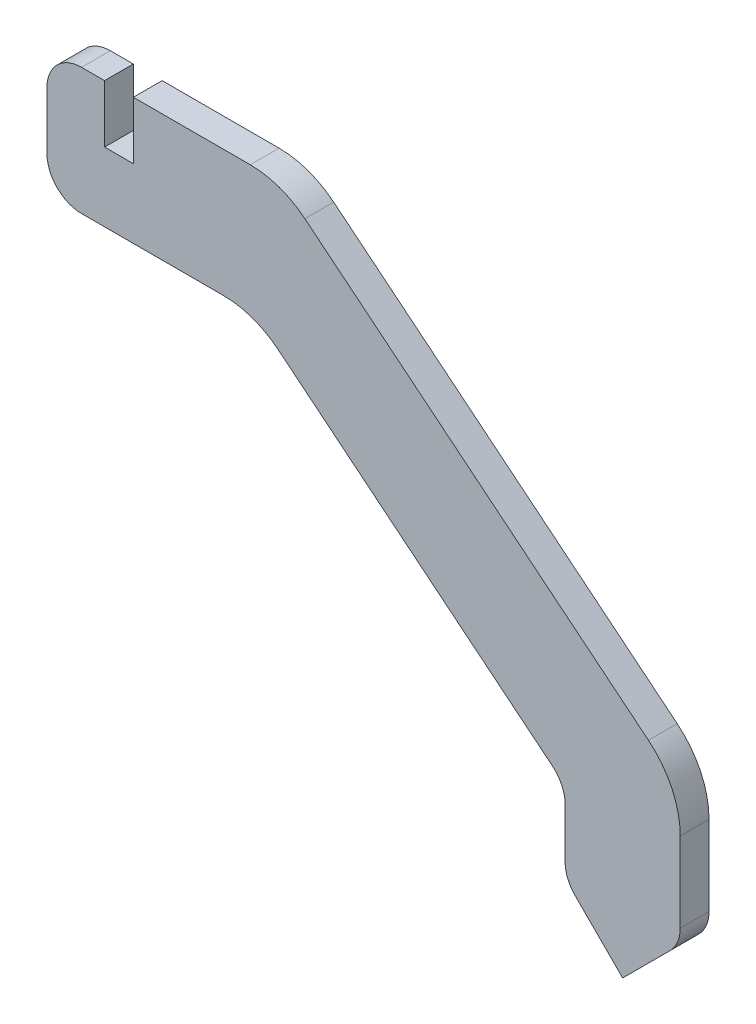
SolidWorks part; units mm, degrees
material "PBT General Purpose"
ref_plane "Front Plane" through (0, 0, 0) normal (0, 0, 1) x (1, 0, 0)
ref_plane "Top Plane" through (0, 0, 0) normal (0, 1, 0) x (1, 0, 0)
ref_plane "Right Plane" through (0, 0, 0) normal (1, 0, 0) x (0, 0, -1)
sketch "frame_outline" plane through (0, 0, 0) normal (0, 0, 1) x (1, 0, 0)
  line L127 (0, 0) -> (0, 1.1)
  line L128 (0, 1.1) -> (0.5, 1.1)
  line L129 (0.5, 1.1) -> (0.5, 0.6)
  line L130 (0.5, 0.6) -> (0.75, 0.6)
  line L131 (0.75, 0.6) -> (0.75, 1.1)
  line L132 (0.75, 1.1) -> (2.0331, 1.1)
  line L133 (2.0331, 1.1) -> (5.5, -1.7249)
  line L134 (5.5, -1.7249) -> (5.5, -2.9)
  line L135 (5.5, -2.9) -> (5, -3.4)
  line L136 (5, -3.4) -> (4.5, -2.9)
  line L137 (4.5, -2.9) -> (4.5, -2.2)
  line L138 (4.5, -2.2) -> (1.8, 0)
  line L139 (1.8, 0) -> (0, 0)
  dimension "D1" = 0.25
  dimension "D2" = 0.5
  dimension "D3" = 0.6
  dimension "D4" = 0.5
  dimension "D5" = 5
  dimension "D6" = 3.4
  dimension "D7" = 1
  dimension "D8" = 1
  dimension "D9" = 0.7
  dimension "D10" = 1.8
extrude "Boss-Extrude1" add sketch "frame_outline" along normal mid plane 0.25
fillet "Fillet1" radius 0.3 5 edges at (5.5, -2.9, 0) (4.5, -2.9, 0) (0, 1.1, 0) (4.5, -2.2, 0) (0, 0, 0)
fillet "Fillet2" radius 0.75 3 edges at (5.5, -1.7249, 0) (2.0331, 1.1, 0) (1.8, 0, 0)
equation "\"t\"= 0.25'thickness of the sheets"
equation "\"t_cf\"= 0.115'thickness of single carbon fiber layer"
equation "\"t_kapton\"= 0.025'thickness of single Kapton flex layer"
equation "\"t_fr4\"= 0.1'thickness of FR4 with copper layer"
equation "\"joint_flex\"= 0.1'Width of flextures gap"
equation "\"joint_flex_eff\"= 0.02'Width of flecture after castelation"
equation "\"joint_fold\"= 0.2'Width of folding joints for 90deg fold"
equation "\"gap_tolerance\"= 0.002'Width to have interfecence fit between carbon fiber inserts"
equation "\"assemble_angle\"= 90'Angle of assembly parts"
equation "\"D1@Boss-Extrude1\"=\"t\""
equation "\"link_lift\"= 0.5'Actuation linkage amplification for the lift motion"
equation "\"link_swing\"= 0.45'Actuation linkage amplification for the swing motion"
equation "\"D1@frame_outline\"=\"t\""
